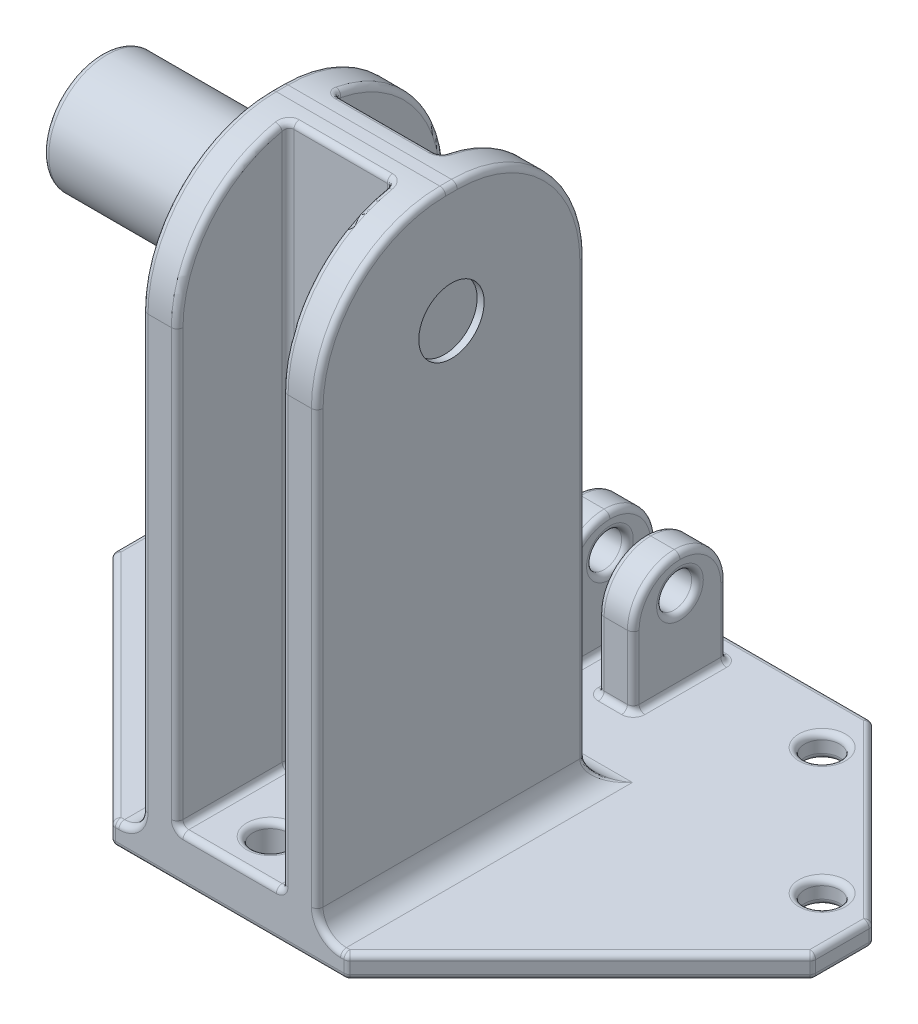
SolidWorks part; units mm, degrees
ref_plane "Front Plane" through (0, 0, 0) normal (0, 0, 1) x (1, 0, 0)
ref_plane "Top Plane" through (0, 0, 0) normal (0, 1, 0) x (1, 0, 0)
ref_plane "Right Plane" through (0, 0, 0) normal (1, 0, 0) x (0, 0, -1)
sketch "Sketch1" plane through (0, 0, 0) normal (0, 1, 0) x (1, 0, 0)
  line L0 (-30, -12.5) -> (-30, 12.5)
  line L1 (-30, 12.5) -> (-15, 27.5)
  line L2 (-15, 27.5) -> (15, 27.5)
  line L3 (15, 27.5) -> (30, 12.5)
  line L4 (30, 12.5) -> (30, -12.5)
  line L5 (30, -12.5) -> (-30, -12.5)
  point P3 (0, -12.5)
  point P8 (0, 27.5)
  point P10 (30, 0)
  dimension "D1" = 45
  dimension "D2" = 60
  dimension "D3" = 25
  dimension "D4" = 15
extrude "Boss-Extrude1" add sketch "Sketch1" along normal blind 2
sketch "Sketch2" plane through (0, 2, 0) normal (0, 1, 0) x (1, 0, 0)
  line L0 (0, 0) -> (0, 27.5) construction
  line L1 (15, 27.5) -> (-15, 27.5) construction
  line L2 (0, 38.2574) -> (-41.2957, -3.0384) construction
  line L3 (0, 38.2574) -> (44.8535, -6.5961) construction
  line L4 (-15, 27.5) -> (-30, 12.5) construction
  line L5 (30, 12.5) -> (15, 27.5) construction
  circle A0 centre (-15.0301, 23.2273) radius 1.5
  circle A1 centre (-25.8488, 12.4086) radius 1.5
  circle A2 centre (15.0301, 23.2273) radius 1.5
  circle A3 centre (25.8488, 12.4086) radius 1.5
  dimension "D2" = 3
  dimension "D3" = 21.2557
  dimension "D1" = 3
  dimension "D4" = 15.3
extrude "Cut-Extrude1" cut sketch "Sketch2" against normal through all
sketch "Sketch3" plane through (0, 2, 0) normal (0, 1, 0) x (1, 0, 0)
  line L0 (0, 0) -> (0, 27.5) construction
  line L1 (15, 27.5) -> (-15, 27.5) construction
  line L3 (-4.5, 17.5764) -> (-1.5, 17.5764)
  line L4 (-4.5, 17.5764) -> (-4.5, 25.5764)
  line L5 (-4.5, 25.5764) -> (-1.5, 25.5764)
  line L6 (-1.5, 17.5764) -> (-1.5, 25.5764)
  line L7 (-4.5, 17.5764) -> (-1.5, 25.5764) construction
  line L8 (-4.5, 25.5764) -> (-1.5, 17.5764) construction
  point P5 (-3, 21.5764)
  dimension "D1" = 3
  dimension "D2" = 8
  dimension "D3" = 1.5
extrude "Boss-Extrude2" add sketch "Sketch3" along normal blind 10
sketch "Sketch4" plane through (-4.5, 0, 0) normal (-1, 0, 0) x (0, 0, 1)
  line L0 (-25.5764, 12) -> (-17.5764, 12) construction
  circle A0 centre (-21.5764, 9) radius 1.5
  point P5 (-21.5764, 12)
  dimension "D2" = 3
  dimension "D1" = 3
extrude "Cut-Extrude2" cut sketch "Sketch4" against normal through all
fillet "Fillet1" radius 4 2 edges at (-3, 12, -17.5764) (-3, 12, -25.5764)
mirror "Mirror2" about plane through (0, 0, 0) normal (1, 0, 0) of "Cut-Extrude2", "Fillet1", "Boss-Extrude2"
sketch "Sketch6" plane through (0, 2, 0) normal (0, 1, 0) x (1, 0, 0)
  line L0 (-30, -12.5) -> (30, -12.5) construction
  line L1 (7.5, 10.5) -> (-7.5, 10.5)
  line L2 (7.5, 10.5) -> (7.5, -12.5)
  line L3 (7.5, -12.5) -> (-7.5, -12.5)
  line L4 (-7.5, 10.5) -> (-7.5, -12.5)
  line L5 (7.5, 10.5) -> (-7.5, -12.5) construction
  line L6 (7.5, -12.5) -> (-7.5, 10.5) construction
  point P0 (0, -1)
  point P8 (0, -12.5)
  dimension "D1" = 23
  dimension "D2" = 15
extrude "Boss-Extrude4" add sketch "Sketch6" along normal blind 50
ref_plane "Plane1" through (0, 0, 1) normal (0, 0, 1) x (1, 0, 0)
sketch "Sketch7" plane through (-7.5, 0, 0) normal (-1, 0, 0) x (0, 0, 1)
  circle A0 centre (1, 42) radius 5
  dimension "D1" = 10
extrude "Boss-Extrude5" add sketch "Sketch7" along normal blind 15
fillet "Fillet2" radius 11 2 edges at (0, 52, -10.5) (0, 52, 12.5)
sketch "Sketch9" plane through (7.5, 0, 0) normal (1, 0, 0) x (0, 0, -1)
  circle A0 centre (-1, 42) radius 2.8
  dimension "D1" = 5.6
extrude "Cut-Extrude4" cut sketch "Sketch9" against normal blind 0.6
chamfer "Chamfer1" distance 20 angle 45 2 edges at (30, 1, 12.5) (-30, 1, 12.5)
ref_plane "Plane2" through (0, 4, 0) normal (0, 1, 0) x (1, 0, 0)
sketch "Sketch8" plane through (0, 4, 0) normal (0, 1, 0) x (1, 0, 0)
  line L0 (7.5, 10.5) -> (-7.5, 10.5) construction
  line L1 (4.5, 10.5) -> (-4.5, 10.5)
  line L2 (4.5, 10.5) -> (4.5, 1)
  line L3 (4.5, 1) -> (-4.5, 1)
  line L4 (-4.5, 10.5) -> (-4.5, 1)
  line L6 (-7.5, 10.5) -> (-7.5, -12.5) construction
  line L7 (7.5, -0.5) -> (7.5, 10.5) construction
  line L8 (-28.6, -1) -> (28.6, -1) construction
  line L9 (7.5, -12.5) -> (-7.5, -12.5) construction
  line L10 (-4.5, -12.5) -> (4.5, -12.5)
  line L11 (-4.5, -12.5) -> (-4.5, -3)
  line L12 (-4.5, -3) -> (4.5, -3)
  line L13 (4.5, -12.5) -> (4.5, -3)
  dimension "D1" = 2
  dimension "D2" = 3
  dimension "D3" = 3
  dimension "D4" = 2
extrude "Cut-Extrude3" cut sketch "Sketch8" along normal through all
sketch "Sketch11" plane through (0, 0, 0) normal (0, -1, 0) x (1, 0, 0)
  circle A0 centre (0, 9.0041) radius 1.52
extrude "Cut-Extrude5" cut sketch "Sketch11" against normal through all contours A0
fillet "Fillet4" radius 2 3 edges at (-7.5, 2, 1) (0, 2, -10.5) (7.5, 2, 1)
fillet "Fillet3" radius 0.5 100 edges at (4.5, 22.5, -10.5) (-4.5, 22.5, -10.5) (-4.5, 22.5, 12.5) (4.5, 22.5, 12.5) (4.5, 48.2284, -7.7916) (-4.5, 48.2284, -7.7916) (-4.5, 48.2284, 9.7916) (4.5, 48.2284, 9.7916) (1.5, 5, -25.5764) (1.5, 10.8284, -24.4049) (1.5, 10.8284, -18.748) (1.5, 5, -17.5764) (1.5, 9, -20.0764) (-1.5, 5, -25.5764) (-1.5, 5, -17.5764) (-1.5, 10.8284, -18.748) (-1.5, 10.8284, -24.4049) (-1.5, 9, -20.0764) (4.5, 5, -25.5764) (4.5, 5, -17.5764) (4.5, 10.8284, -18.748) (4.5, 10.8284, -24.4049) (4.5, 9, -20.0764) (-4.5, 5, -25.5764) (-4.5, 10.8284, -24.4049) (-4.5, 10.8284, -18.748) (-4.5, 5, -17.5764) (-4.5, 9, -20.0764) (0, 51.8972, -1) (-4.5, 27.9486, -1) (0, 4, -1) (4.5, 27.9486, -1) (0, 51.8972, 3) (4.5, 27.9486, 3) (0, 4, 3) (-4.5, 27.9486, 3) (-22.5, 42, 6) (-7.5, 22.5, 12.5) (-7.5, 22.5, -10.5) (-7.5, 48.7782, -7.2782) (-7.5, 48.7782, 9.2782) (7.5, 22.5, 12.5) (7.5, 48.7782, 9.2782) (7.5, 48.7782, -7.2782) (7.5, 22.5, -10.5) (15, 1, -27.5) (-15, 1, -27.5) (30, 1, -12.5) (30, 1, -7.5) (22.5, 0, -20) (0, 0, -27.5) (-22.5, 0, -20) (-30, 0, -10) (-20, 0, 2.5) (0, 0, 12.5) (20, 0, 2.5) (30, 0, -10) (-15.0301, 0, -21.7273) (-25.8488, 0, -10.9086) (15.0301, 0, -21.7273) (25.8488, 0, -10.9086) (-9.75, 2, 12.5) (-20, 2, 2.5) (-30, 2, -10) (-22.5, 2, -20) (0, 2, -27.5) (22.5, 2, -20) (30, 2, -10) (20, 2, 2.5) (9.75, 2, 12.5) (4.5, 2, -21.5764) (3, 2, -25.5764) (1.5, 2, -21.5764) (3, 2, -17.5764) (-15.0301, 2, -21.7273) (-25.8488, 2, -10.9086) (15.0301, 2, -21.7273) (25.8488, 2, -10.9086) (-3, 2, -25.5764) (-4.5, 2, -21.5764) (-3, 2, -17.5764) (-1.5, 2, -21.5764) (10, 1, 12.5) (-10, 1, 12.5) (-30, 1, -7.5) (-30, 1, -12.5) (-7.5, 52, 1) (7.5, 52, 1) (0, 0, 7.4841) (0, 4, 7.4841) (8.0858, 2.5858, -11.0858) (8.0858, 2.5858, 12.5) (-8.0858, 2.5858, -11.0858) (-8.0858, 2.5858, 12.5) (-4.5, 4, 7.75) (4.5, 4, 7.75) (0, 4, 12.5) (-4.5, 4, -5.75) (4.5, 4, -5.75) (0, 4, -10.5)
fillet "Fillet5" radius 2 1 edges at (-7.5, 42, -4)
